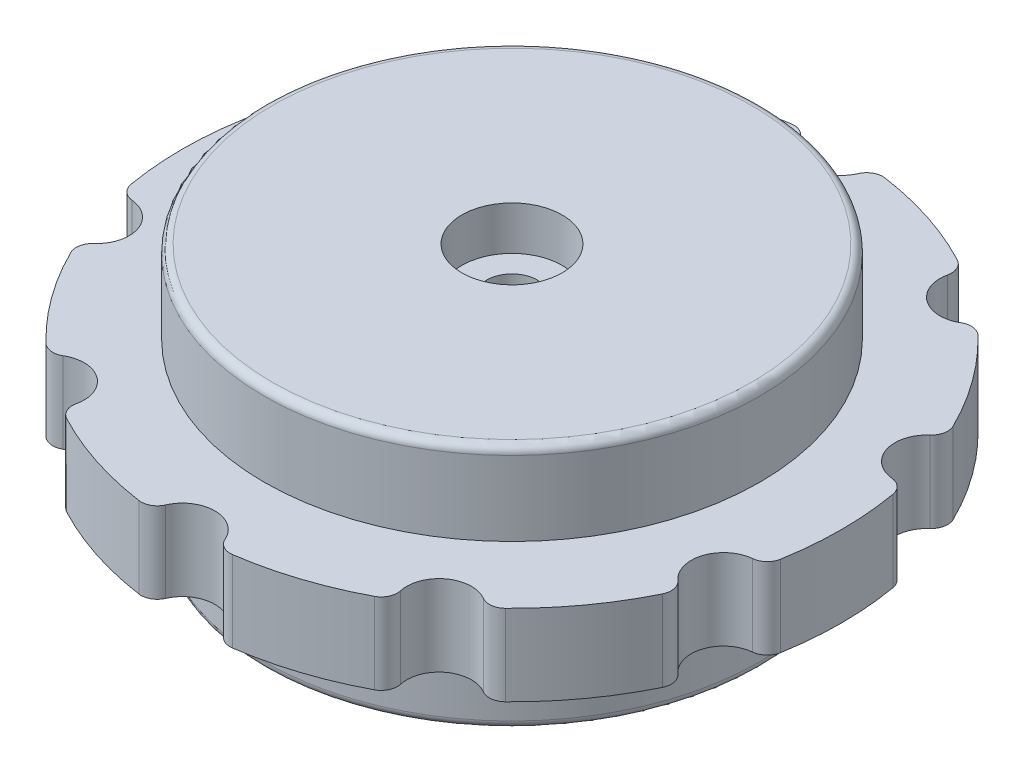
SolidWorks part; units mm, degrees
ref_plane "前视基准面" through (0, 0, 0) normal (0, 0, 1) x (1, 0, 0)
ref_plane "上视基准面" through (0, 0, 0) normal (0, 1, 0) x (1, 0, 0)
ref_plane "右视基准面" through (0, 0, 0) normal (1, 0, 0) x (0, 0, -1)
other "Configuration Table"
sketch "草图1" plane through (0, 0, 0) normal (0, 1, 0) x (1, 0, 0)
  circle A0 centre (0, 0) radius 15.3
  circle A1 centre (0, 0) radius 20.35
  circle A2 centre (0, 0) radius 13.7
  circle A3 centre (0, 20.35) radius 2
  dimension "D1" = 30.6
  dimension "D2" = 40.7
  dimension "D3" = 1.6
  dimension "D4" = 4
extrude "凸台-拉伸1" add sketch "草图1" along normal mid plane 15.2 contours A0 | A2
extrude "凸台-拉伸2" add sketch "草图1<3>" along normal mid plane 5 contours A1
sketch "草图1<3>" plane through (0, 0, 0) normal (0, 1, 0) x (1, 0, 0) same geometry as "草图1"
extrude "切除-拉伸1" cut sketch "草图1<4>" against normal through all both and the other way through all contours A3
sketch "草图1<4>" plane through (0, 0, 0) normal (0, 1, 0) x (1, 0, 0) same geometry as "草图1"
fillet "圆角1" radius 1 2 edges at (1.9976, 0, -20.2517) (-1.9976, 0, -20.2517)
pattern_circular "阵列(圆周)1" count 10 over 360 about axis through (0, 2.5, 0) along (0, -1, 0) of "切除-拉伸1", "圆角1"
fillet "圆角2" radius 0.5 2 edges at (0, -7.6, 15.3) (0, 7.6, 15.3)
extrude "凸台-拉伸3" add sketch "草图1<5>" along normal mid plane 7.8 contours A2
sketch "草图1<5>" plane through (0, 0, 0) normal (0, 1, 0) x (1, 0, 0) same geometry as "草图1"
extrude "凸台-拉伸5" add sketch "草图1<6>" along normal up to surface (7.6 mm away) from surface contours A2 up to face at (0, 7.6, 14.8) starting at face at (0, -7.6, 14.8)
sketch "草图1<6>" plane through (0, 0, 0) normal (0, 1, 0) x (1, 0, 0) same geometry as "草图1"
sketch "草图2" plane through (0, 2.5, 0) normal (0, 1, 0) x (1, 0, 0)
  line L0 (0, 20.35) -> (11.9614, 16.4635)
  line L1 (-11.9614, 16.4635) -> (0, 20.35)
  arc A0 (-1.834, 19.5523) -> (1.834, 19.5523) centre (0, 20.35) ccw construction
  arc A1 (10.0088, 16.8962) -> (12.9763, 14.7401) centre (11.9614, 16.4635) ccw construction
  arc A2 (-12.9763, 14.7401) -> (-10.0088, 16.8962) centre (-11.9614, 16.4635) ccw construction
  dimension "D1" = 12.577
  dimension "D2" = 12.577
sketch "草图4" plane through (0, -7.6, 0) normal (0, -1, 0) x (1, 0, 0)
  line L0 (1, 1.1843) -> (1, -1.1843)
  circle A0 centre (0, 0) radius 1.55
  circle A1 centre (0, 0) radius 3.1
  dimension "D1" = 3.1
  dimension "D2" = 6.2
  dimension "D3" = 1
extrude "切除-拉伸3" cut sketch "草图4" against normal through all contours A0
extrude "切除-拉伸4" cut sketch "草图4<3>" against normal blind 2.7 contours A1
sketch "草图4<3>" plane through (0, -7.6, 0) normal (0, -1, 0) x (1, 0, 0) same geometry as "草图4"
extrude "切除-拉伸5" cut sketch "草图4<4>" along normal blind 2.7 from surface contours A1 starting at face at (0, 7.6, -1.55)
sketch "草图4<4>" plane through (0, -7.6, 0) normal (0, -1, 0) x (1, 0, 0) same geometry as "草图4"
